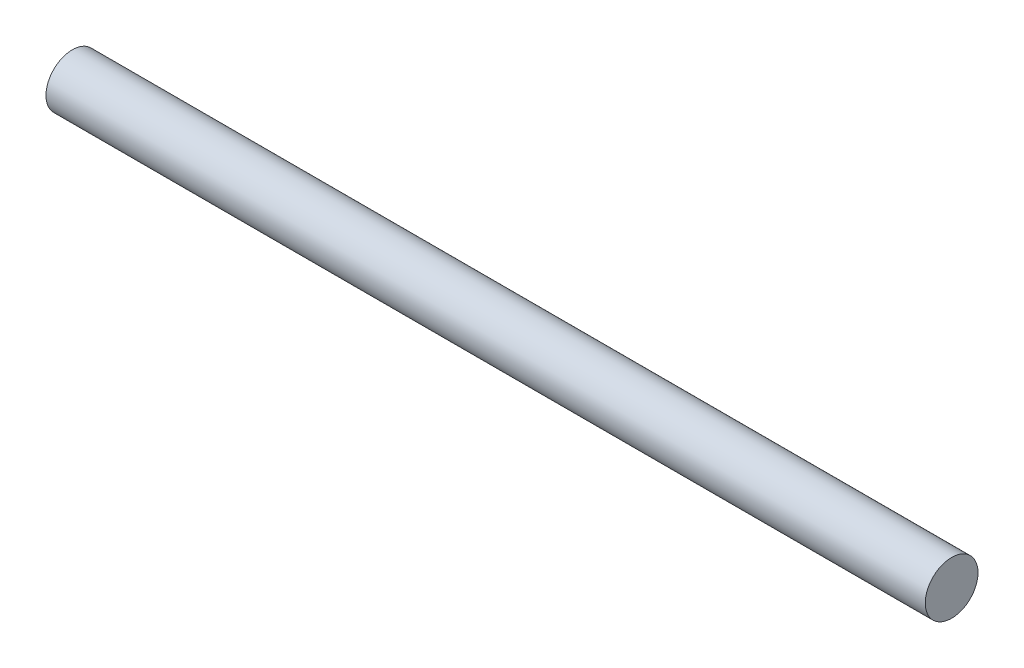
SolidWorks part; units mm, degrees
material "2024 Alloy"
ref_plane "Front Plane" through (0, 0, 0) normal (0, 0, 1) x (1, 0, 0)
ref_plane "Top Plane" through (0, 0, 0) normal (0, 1, 0) x (1, 0, 0)
ref_plane "Right Plane" through (0, 0, 0) normal (1, 0, 0) x (0, 0, -1)
sketch "Sketch1" plane through (0, 0, 0) normal (1, 0, 0) x (0, 0, -1)
  circle A0 centre (0, 0) radius 1.5
  dimension "D1" = 3
extrude "Boss-Extrude1" add sketch "Sketch1" along normal blind 25 and the other way blind 25
